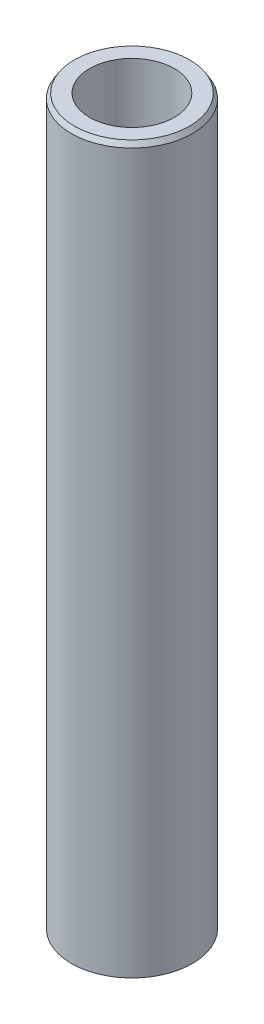
SolidWorks part; units mm, degrees
ref_plane "Front Plane" through (0, 0, 0) normal (0, 0, 1) x (1, 0, 0)
ref_plane "Top Plane" through (0, 0, 0) normal (0, 1, 0) x (1, 0, 0)
ref_plane "Right Plane" through (0, 0, 0) normal (1, 0, 0) x (0, 0, -1)
sketch "Sketch1" plane through (0, 0, 0) normal (0, 1, 0) x (1, 0, 0)
  circle A0 centre (0, 0) radius 50
  dimension "SHAFT_OD" = 100
extrude "Boss-Extrude1" add sketch "Sketch1" along normal blind 600
sketch "Sketch2" plane through (0, 0, 0) normal (0, 1, 0) x (1, 0, 0)
  circle A0 centre (0, 0) radius 34.9818
  dimension "BORE_D" = 69.9637
extrude "Cut-Extrude1" cut sketch "Sketch2" along normal through all
chamfer "Chamfer1" distance 4.06 angle 31.692 2 edges at (0, 600, 50) (0, 0, 50) first distance on face at (0, 600, 50) first distance on face at (0, 0, 34.9818)
